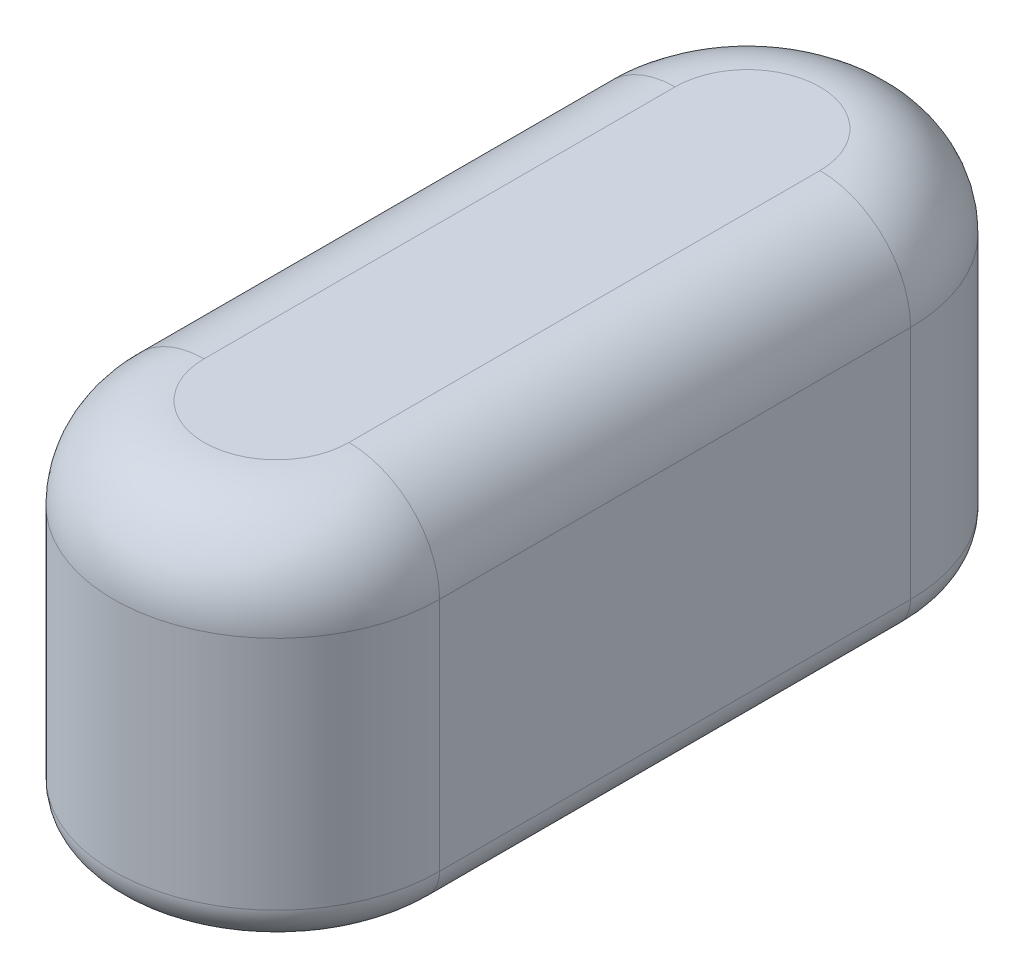
SolidWorks part; units mm, degrees
material "6061 Alloy"
ref_plane "Front Plane" through (0, 0, 0) normal (0, 0, 1) x (1, 0, 0)
ref_plane "Top Plane" through (0, 0, 0) normal (0, 1, 0) x (1, 0, 0)
ref_plane "Right Plane" through (0, 0, 0) normal (1, 0, 0) x (0, 0, -1)
sketch "Sketch1" plane through (0, 0, 0) normal (0, 0, 1) x (1, 0, 0)
  line L0 (0, 12.7) -> (177.8, 12.7)
  line L5 (0, 0) -> (177.8, 0)
  line L6 (0, 0) -> (0, 508) construction
  line L7 (0, 508) -> (101.6, 508)
  line L8 (228.6, 50.8) -> (228.6, 381)
  line L9 (215.9, 50.8) -> (215.9, 381)
  line L10 (0, 495.3) -> (101.6, 495.3)
  line L11 (0, 0) -> (0, 12.7)
  line L12 (0, 508) -> (0, 495.3)
  arc A0 (177.8, 0) -> (228.6, 50.8) centre (177.8, 50.8) ccw
  arc A1 (101.6, 508) -> (228.6, 381) centre (101.6, 381) cw
  arc A2 (177.8, 12.7) -> (215.9, 50.8) centre (177.8, 50.8) ccw
  arc A3 (101.6, 495.3) -> (215.9, 381) centre (101.6, 381) cw
  point P6 (228.6, 0)
  point P10 (228.6, 508)
  dimension "D3" = 50.8
  dimension "D4" = 127
  dimension "D1" = 228.6
  dimension "D2" = 508
  dimension "D5" = 12.7
extrude "Boss-Extrude1" add sketch "Sketch1" along normal blind 330.2
revolve "Revolve1" add sketch "Sketch1<2>" angle 90 about L6
sketch "Sketch1<2>" plane through (0, 0, 0) normal (0, 0, 1) x (1, 0, 0) same geometry as "Sketch1"
mirror "Mirror1" about plane through (0, 0, 0) normal (1, 0, 0) of "Boss-Extrude1", "Revolve1"
mirror "Mirror2" about plane through (177.8, 50.8, 330.2) normal (0, 0, 1) of "Boss-Extrude1", "Revolve1", "Mirror1"
